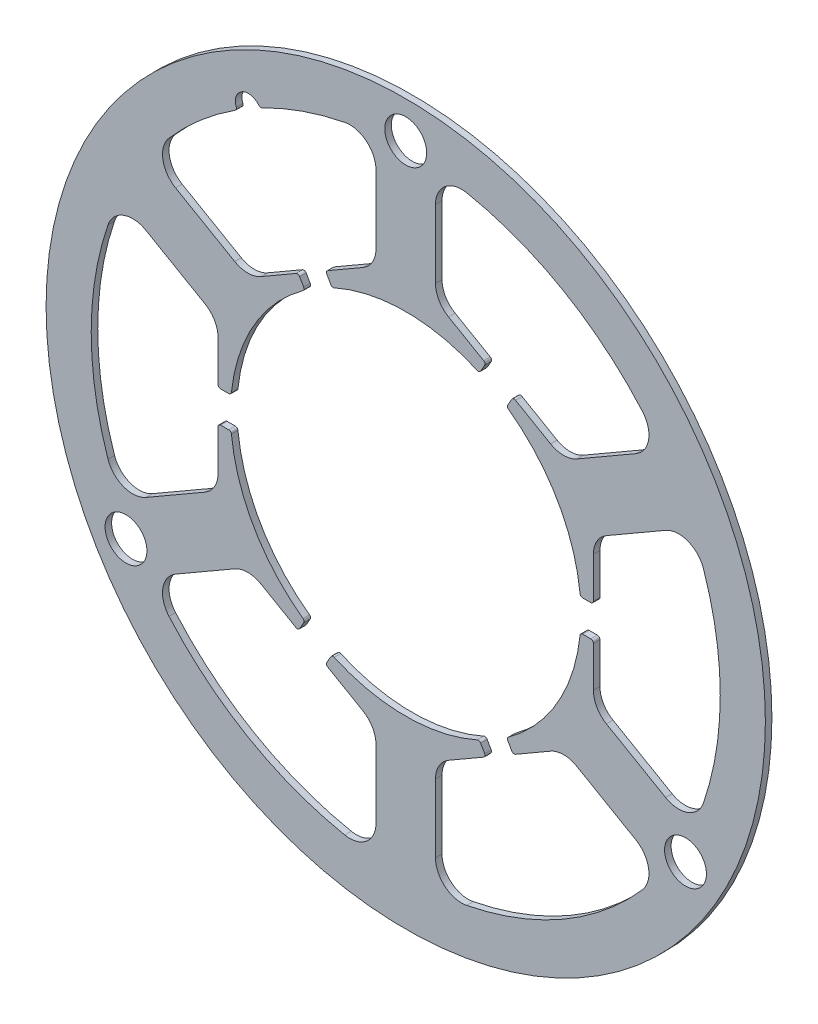
SolidWorks part; units mm, degrees
ref_plane "Ön Düzlem" through (0, 0, 0) normal (0, 0, 1) x (1, 0, 0)
ref_plane "Üst Düzlem" through (0, 0, 0) normal (0, 1, 0) x (1, 0, 0)
ref_plane "Sağ Düzlem" through (0, 0, 0) normal (1, 0, 0) x (0, 0, -1)
sketch "Çizim1" plane through (0, 0, 0) normal (0, 0, 1) x (1, 0, 0)
  line L0 (5.9625, 13.1275) -> (3.275, 14.6791)
  line L1 (3.275, -14.6791) -> (5.9625, -13.1275)
  line L2 (14.35, -4.5033) -> (14.35, -1.4)
  line L3 (11.075, 10.1758) -> (8.3874, 11.7275)
  line L4 (-3.275, 14.6791) -> (-5.9625, 13.1275)
  line L5 (-14.35, 4.5033) -> (-14.35, 1.4001)
  line L6 (-11.075, -10.1758) -> (-8.3876, -11.7274)
  line L8 (8.3873, -11.7275) -> (11.075, -10.1758)
  line L9 (-5.9627, -13.1274) -> (-3.275, -14.6791)
  line L10 (-14.35, -1.3999) -> (-14.35, -4.5033)
  line L11 (-2.275, 16.4112) -> (-2.275, 21.6316)
  line L12 (-8.1142, 11.6543) -> (-7.8031, 11.1154)
  line L13 (-6.0357, 12.8543) -> (-5.7246, 12.3154)
  line L14 (6.0357, 12.8543) -> (5.7246, 12.3154)
  line L15 (8.1142, 11.6543) -> (7.8031, 11.1154)
  line L16 (14.15, 1.2) -> (13.5278, 1.2)
  line L17 (14.15, -1.2) -> (13.5277, -1.2)
  line L18 (8.1141, -11.6543) -> (7.803, -11.1154)
  line L19 (6.0357, -12.8543) -> (5.7245, -12.3154)
  line L20 (-6.0359, -12.8542) -> (-5.7248, -12.3153)
  line L21 (-8.1144, -11.6542) -> (-7.8032, -11.1153)
  line L22 (-14.15, -1.1999) -> (-13.5278, -1.1999)
  line L23 (-14.15, 1.2001) -> (-13.5277, 1.2001)
  line L24 (-8.3874, 11.7275) -> (-11.075, 10.1758)
  line L25 (14.35, 1.4) -> (14.35, 4.5033)
  line L26 (2.275, 16.4112) -> (2.275, 21.6316)
  line L27 (13.075, 10.1758) -> (17.596, 12.786)
  line L28 (15.35, 6.2354) -> (19.871, 8.8456)
  line L29 (15.35, -6.2354) -> (19.871, -8.8456)
  line L30 (13.075, -10.1758) -> (17.596, -12.786)
  line L31 (2.275, -16.4112) -> (2.275, -21.6316)
  line L32 (-2.275, -16.4112) -> (-2.275, -21.6316)
  line L33 (-13.075, -10.1758) -> (-17.596, -12.786)
  line L34 (-15.35, -6.2354) -> (-19.871, -8.8456)
  line L35 (-15.35, 6.2354) -> (-19.871, 8.8456)
  line L36 (-13.075, 10.1758) -> (-17.596, 12.786)
  circle A0 centre (0, 0) radius 27.5
  arc A1 (-4.6628, 23.5937) -> (-10.9904, 21.3919) centre (0, 0) ccw
  arc A3 (-7.859, 10.8534) -> (-13.3288, 1.3795) centre (0, 0) ccw
  arc A4 (5.4698, 12.2328) -> (-5.4698, 12.2328) centre (0, 0) ccw
  arc A7 (13.3288, 1.3794) -> (7.859, 10.8534) centre (0, 0) ccw
  arc A8 (7.8589, -10.8535) -> (13.3288, -1.3794) centre (0, 0) ccw
  arc A10 (-5.47, -12.2327) -> (5.4697, -12.2328) centre (0, 0) ccw
  arc A12 (-13.3288, -1.3793) -> (-7.8591, -10.8533) centre (0, 0) ccw
  arc A14 (18.1013, 15.8349) -> (4.6628, 23.5937) centre (0, 0) ccw
  arc A15 (22.7641, -7.7588) -> (22.7641, 7.7588) centre (0, 0) ccw
  arc A16 (4.6628, -23.5937) -> (18.1013, -15.8349) centre (0, 0) ccw
  arc A17 (-18.1013, -15.8349) -> (-4.6628, -23.5937) centre (0, 0) ccw
  arc A18 (-22.7641, 7.7588) -> (-22.7641, -7.7588) centre (0, 0) ccw
  arc A19 (-15.35, 6.2354) -> (-14.35, 4.5033) centre (-16.35, 4.5033) cw
  arc A20 (-19.871, 8.8456) -> (-22.7641, 7.7588) centre (-20.871, 7.1136) ccw
  arc A21 (-15.35, -6.2354) -> (-14.35, -4.5033) centre (-16.35, -4.5033) ccw
  arc A22 (-19.871, -8.8456) -> (-22.7641, -7.7588) centre (-20.871, -7.1136) cw
  arc A23 (-13.075, -10.1758) -> (-11.075, -10.1758) centre (-12.075, -11.9078) cw
  arc A24 (-17.596, -12.786) -> (-18.1013, -15.8349) centre (-16.596, -14.5181) ccw
  arc A25 (-2.275, -16.4112) -> (-3.275, -14.6791) centre (-4.275, -16.4112) ccw
  arc A26 (-2.275, -21.6316) -> (-4.6628, -23.5937) centre (-4.275, -21.6316) cw
  arc A27 (2.275, -16.4112) -> (3.275, -14.6791) centre (4.275, -16.4112) cw
  arc A28 (2.275, -21.6316) -> (4.6628, -23.5937) centre (4.275, -21.6316) ccw
  arc A29 (13.075, -10.1758) -> (11.075, -10.1758) centre (12.075, -11.9078) ccw
  arc A30 (17.596, -12.786) -> (18.1013, -15.8349) centre (16.596, -14.5181) cw
  arc A31 (15.35, -6.2354) -> (14.35, -4.5033) centre (16.35, -4.5033) cw
  arc A32 (19.871, -8.8456) -> (22.7641, -7.7588) centre (20.871, -7.1136) ccw
  arc A33 (19.871, 8.8456) -> (22.7641, 7.7588) centre (20.871, 7.1136) cw
  arc A34 (15.35, 6.2354) -> (14.35, 4.5033) centre (16.35, 4.5033) ccw
  arc A35 (13.075, 10.1758) -> (11.075, 10.1758) centre (12.075, 11.9078) cw
  arc A36 (17.596, 12.786) -> (18.1013, 15.8349) centre (16.596, 14.5181) ccw
  arc A37 (2.275, 16.4112) -> (3.275, 14.6791) centre (4.275, 16.4112) ccw
  arc A38 (2.275, 21.6316) -> (4.6628, 23.5937) centre (4.275, 21.6316) cw
  arc A39 (-2.275, 16.4112) -> (-3.275, 14.6791) centre (-4.275, 16.4112) cw
  arc A40 (-13.075, 10.1758) -> (-11.075, 10.1758) centre (-12.075, 11.9078) ccw
  arc A41 (-17.596, 12.786) -> (-18.1013, 15.8349) centre (-16.596, 14.5181) cw
  arc A42 (-2.275, 21.6316) -> (-4.6628, 23.5937) centre (-4.275, 21.6316) ccw
  circle A43 centre (0, 24.7) radius 1.6
  circle A44 centre (21.3908, -12.35) radius 1.6
  circle A45 centre (-21.3908, -12.35) radius 1.6
  arc A46 (-11.239, 21.4461) -> (-12.9534, 20.4563) centre (-12.025, 20.8279) ccw
  arc A47 (-13.0307, 20.2139) -> (-18.1013, 15.8349) centre (0, 0) ccw
  arc A48 (-13.5277, 1.2001) -> (-13.3288, 1.3795) centre (-13.5277, 1.4001) ccw
  arc A49 (-14.35, 1.4001) -> (-14.15, 1.2001) centre (-14.15, 1.4001) ccw
  arc A50 (-14.35, -1.3999) -> (-14.15, -1.1999) centre (-14.15, -1.3999) cw
  arc A51 (-13.5278, -1.1999) -> (-13.3288, -1.3793) centre (-13.5278, -1.3999) cw
  arc A52 (-8.3876, -11.7274) -> (-8.1144, -11.6542) centre (-8.2876, -11.5542) ccw
  arc A53 (-7.8032, -11.1153) -> (-7.8591, -10.8533) centre (-7.9764, -11.0153) ccw
  arc A54 (-5.9627, -13.1274) -> (-6.0359, -12.8542) centre (-5.8627, -12.9542) cw
  arc A55 (-5.7248, -12.3153) -> (-5.47, -12.2327) centre (-5.5516, -12.4153) cw
  arc A56 (5.7245, -12.3154) -> (5.4697, -12.2328) centre (5.5513, -12.4154) ccw
  arc A57 (5.9625, -13.1275) -> (6.0357, -12.8543) centre (5.8625, -12.9543) ccw
  arc A58 (8.3873, -11.7275) -> (8.1141, -11.6543) centre (8.2873, -11.5543) cw
  arc A59 (7.803, -11.1154) -> (7.8589, -10.8535) centre (7.9762, -11.0154) cw
  arc A60 (14.35, -1.4) -> (14.15, -1.2) centre (14.15, -1.4) ccw
  arc A61 (13.5277, -1.2) -> (13.3288, -1.3794) centre (13.5277, -1.4) ccw
  arc A62 (13.5278, 1.2) -> (13.3288, 1.3794) centre (13.5278, 1.4) cw
  arc A63 (14.35, 1.4) -> (14.15, 1.2) centre (14.15, 1.4) cw
  arc A64 (7.8031, 11.1154) -> (7.859, 10.8534) centre (7.9763, 11.0154) ccw
  arc A65 (8.3874, 11.7275) -> (8.1142, 11.6543) centre (8.2874, 11.5543) ccw
  arc A66 (5.7246, 12.3154) -> (5.4698, 12.2328) centre (5.5514, 12.4154) cw
  arc A67 (6.0357, 12.8543) -> (5.9625, 13.1275) centre (5.8625, 12.9543) ccw
  arc A68 (-5.9625, 13.1275) -> (-6.0357, 12.8543) centre (-5.8625, 12.9543) ccw
  arc A69 (-5.7246, 12.3154) -> (-5.4698, 12.2328) centre (-5.5514, 12.4154) ccw
  arc A70 (-7.8031, 11.1154) -> (-7.859, 10.8534) centre (-7.9763, 11.0154) cw
  arc A71 (-8.3874, 11.7275) -> (-8.1142, 11.6543) centre (-8.2874, 11.5543) cw
  arc A72 (-12.9534, 20.4563) -> (-13.0307, 20.2139) centre (-13.1391, 20.382) cw
  arc A73 (-11.239, 21.4461) -> (-10.9904, 21.3919) centre (-11.0818, 21.5698) ccw
  point P29 (0, 0)
  point P51 (-0.0001, 0)
  point P72 (0, 0)
  point P123 (0, 0)
  point P173 (-6.1357, 13.0275)
  point P176 (-5.6338, 12.1581)
  point P179 (-7.7123, 10.9581)
  point P182 (-8.2142, 11.8275)
  point P185 (-12.8804, 20.31)
  dimension "D1" = 55
  dimension "D2" = 48.1
  dimension "D4" = 26.8
  dimension "D12" = 2
  dimension "D13" = 3.2
  dimension "D14" = 1.2
  dimension "D16" = 2
  dimension "D18" = 0.2
  dimension "D3" = 28.7
  dimension "D5" = 2.4
  dimension "D7" = 6
  dimension "D8" = 2.275
  dimension "D6" = 2.4
  dimension "D9" = 4.55
  dimension "D10" = 120
  dimension "D11" = 6
  dimension "D17" = 30
  dimension "D19" = 2.4
  dimension "D20" = 2.4
  dimension "D15" = 3
extrude "Yükseklik-Ekstrüzyon1" add sketch "Çizim1" along normal blind 0.5
